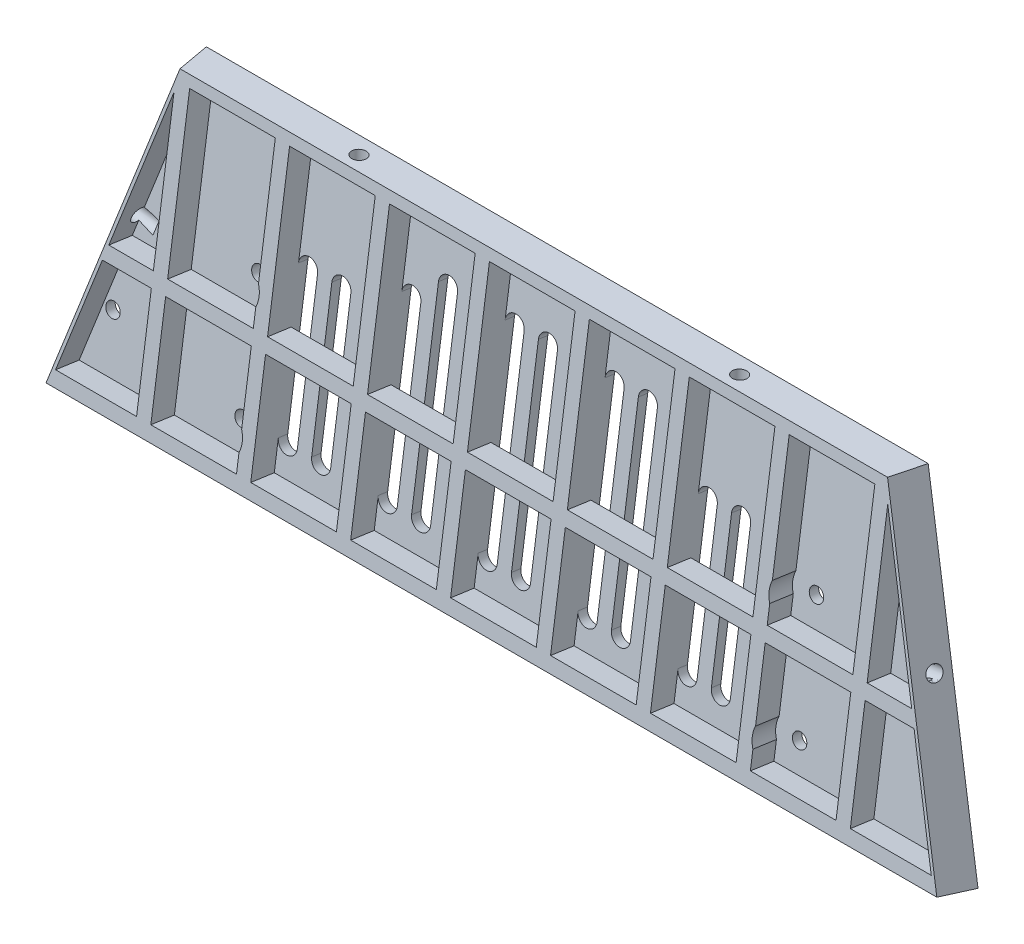
SolidWorks part; units mm, degrees
material "ABS"
ref_plane "前视基准面" through (0, 0, 0) normal (0, 0, 1) x (1, 0, 0)
ref_plane "上视基准面" through (0, 0, 0) normal (0, 1, 0) x (1, 0, 0)
ref_plane "右视基准面" through (0, 0, 0) normal (1, 0, 0) x (0, 0, -1)
other "Configuration Table"
sketch "草图1" plane through (0, 0, 0) normal (0, 0, 1) x (1, 0, 0)
  line L0 (145, -15) -> (145, -95)
  line L1 (145, -95) -> (-145, -95)
  line L2 (-145, -95) -> (-145, -15)
  line L3 (-145, -15) -> (-85, 215)
  line L4 (-85, 215) -> (85, 215)
  line L5 (85, 215) -> (145, -15)
  line L6 (0, 215) -> (0, -95) construction
  arc A0 (145, -95) -> (-145, -95) centre (0, 951.25) cw construction
  point P11 (0, -105)
  dimension "D4" = 320
  dimension "D1" = 10
  dimension "D2" = 290
  dimension "D3" = 80
  dimension "D5" = 170
  dimension "D6" = 95
extrude "凸台-拉伸1" add sketch "草图1" against normal blind 70
chamfer "倒角1" distance 70 angle 18 4 edges at (115, 100, -70) (145, -55, -70) (-115, 100, -70) (-145, -55, -70)
sketch "草图2" plane through (0, 0, 0) normal (1, 0, 0) x (0, 0, -1)
  line L0 (10, 215) -> (0, 145)
  line L1 (70, 215) -> (0, 215) construction
  line L2 (0, 215) -> (0, -15) construction
  line L3 (0, 145) -> (0, 215)
  line L4 (0, 215) -> (10, 215)
  dimension "D1" = 70
  dimension "D2" = 10
extrude "切除-拉伸1" cut sketch "草图2" against normal through all and the other way through all
chamfer "倒角2" distance 20 distance2 60 1 edges at (0, 215, -70)
sketch "草图12" plane through (0, 2.9, 20.3) normal (0, 0.1414, 0.9899) x (1, 0, 0)
  line L4 (103.2609, 143.5427) -> (81.6421, 214.2534)
  line L5 (81.6421, 214.2534) -> (-81.6421, 214.2534)
  line L7 (-103.2609, 143.5427) -> (103.2609, 143.5427)
  line L9 (81.6421, 214.2534) -> (-81.6421, 214.2534)
  line L11 (-103.2609, 143.5427) -> (103.2609, 143.5427)
  line L12 (103.2609, 143.5427) -> (81.6421, 214.2534)
  line L14 (-81.6421, 214.2534) -> (-103.2609, 143.5427)
  line L15 (-81.6421, 214.2534) -> (-103.2609, 143.5427)
  dimension "D1" = 0
extrude "切除-拉伸10" cut sketch "草图12" against normal blind 110 flip side to cut
sketch "草图13" plane through (0, 2.9, 20.3) normal (0, 0.1414, 0.9899) x (1, 0, 0)
  line L4 (103.2609, 143.5427) -> (81.6421, 214.2534)
  line L5 (81.6421, 214.2534) -> (-81.6421, 214.2534)
  line L7 (-103.2609, 143.5427) -> (103.2609, 143.5427)
  line L9 (81.6421, 214.2534) -> (-81.6421, 214.2534)
  line L11 (-103.2609, 143.5427) -> (103.2609, 143.5427)
  line L12 (103.2609, 143.5427) -> (81.6421, 214.2534)
  line L14 (-81.6421, 214.2534) -> (-103.2609, 143.5427)
  line L15 (-81.6421, 214.2534) -> (-103.2609, 143.5427)
  dimension "D1" = 0
extrude "切除-拉伸11" cut sketch "草图13" against normal blind 110 from offset 2 offset against normal yes
sketch "草图14" plane through (0, 2.9, 20.3) normal (0, 0.1414, 0.9899) x (1, 0, 0)
  line L4 (-76.5908, 210.2534) -> (-96.0695, 146.5427)
  line L5 (-96.0695, 146.5427) -> (96.0695, 146.5427)
  line L6 (96.0695, 146.5427) -> (76.5908, 210.2534)
  line L7 (76.5908, 210.2534) -> (-76.5908, 210.2534)
  line L8 (-103.2609, 143.5427) -> (103.2609, 143.5427) construction
  line L9 (81.6421, 214.2534) -> (-81.6421, 214.2534) construction
  line L11 (103.2609, 143.5427) -> (81.6421, 214.2534) construction
  line L23 (0, 214.2534) -> (0, 143.5427) construction
  dimension "D1" = 3
  dimension "D2" = 4
  dimension "D3" = 6
extrude "切除-拉伸12" cut sketch "草图14" against normal blind 110 flip side to cut
sketch "草图15" plane through (0, 2.9, 20.3) normal (0, 0.1414, 0.9899) x (1, 0, 0)
  line L0 (0, 210.2534) -> (0, 146.5427) construction
  line L1 (76.5908, 210.2534) -> (-76.5908, 210.2534) construction
  line L2 (-96.0695, 146.5427) -> (96.0695, 146.5427) construction
  line L3 (77.7153, 189.4741) -> (86.4866, 160.785) construction
  line L4 (-25, 205.2534) -> (25, 205.2534) construction
  line L5 (96.0695, 146.5427) -> (76.5908, 210.2534) construction
  line L6 (76.5908, 210.2534) -> (71.8093, 208.7915) construction
  line L7 (71.8093, 208.7915) -> (77.7153, 189.4741) construction
  line L8 (0, 195.5427) -> (0, 155.5427) construction
  line L9 (2, 195.5427) -> (2, 155.5427)
  line L10 (-2, 195.5427) -> (-2, 155.5427)
  line L11 (7, 155.5427) -> (7, 195.5427) construction
  line L12 (5, 155.5427) -> (5, 195.5427)
  line L13 (9, 155.5427) -> (9, 195.5427)
  line L14 (14, 155.5427) -> (14, 195.5427) construction
  line L15 (12, 155.5427) -> (12, 195.5427)
  line L16 (16, 155.5427) -> (16, 195.5427)
  line L17 (21, 155.5427) -> (21, 195.5427) construction
  line L18 (19, 155.5427) -> (19, 195.5427)
  line L19 (23, 155.5427) -> (23, 195.5427)
  line L20 (28, 155.5427) -> (28, 190.5427) construction
  line L21 (26, 155.5427) -> (26, 190.5427)
  line L22 (30, 155.5427) -> (30, 190.5427)
  line L23 (35, 155.5427) -> (35, 185.5427) construction
  line L24 (33, 155.5427) -> (33, 185.5427)
  line L25 (37, 155.5427) -> (37, 185.5427)
  line L26 (42, 185.5427) -> (42, 155.5427) construction
  line L27 (44, 185.5427) -> (44, 155.5427)
  line L28 (40, 185.5427) -> (40, 155.5427)
  line L29 (49, 185.5427) -> (49, 155.5427) construction
  line L30 (51, 185.5427) -> (51, 155.5427)
  line L31 (47, 185.5427) -> (47, 155.5427)
  line L32 (21, 195.5427) -> (35, 185.5427) construction
  line L33 (0, 195.5427) -> (7, 195.5427) construction
  line L34 (7, 195.5427) -> (14, 195.5427) construction
  line L35 (14, 195.5427) -> (21, 195.5427) construction
  line L36 (35, 185.5427) -> (42, 185.5427) construction
  line L37 (42, 185.5427) -> (49, 185.5427) construction
  line L38 (35, 185.5427) -> (28, 185.5427) construction
  line L39 (28, 185.5427) -> (21, 185.5427) construction
  line L40 (0, 155.5427) -> (7, 155.5427) construction
  line L41 (7, 155.5427) -> (14, 155.5427) construction
  line L42 (14, 155.5427) -> (21, 155.5427) construction
  line L43 (21, 155.5427) -> (28, 155.5427) construction
  line L44 (28, 155.5427) -> (35, 155.5427) construction
  line L45 (35, 155.5427) -> (42, 155.5427) construction
  line L46 (42, 155.5427) -> (49, 155.5427) construction
  line L47 (-2, 175.5427) -> (2, 175.5427) construction
  line L48 (5, 175.5427) -> (9, 175.5427) construction
  line L49 (12, 175.5427) -> (16, 175.5427) construction
  line L50 (19, 175.5427) -> (23, 175.5427) construction
  line L51 (26, 173.0427) -> (30, 173.0427) construction
  line L52 (33, 170.5427) -> (37, 170.5427) construction
  line L53 (40, 170.5427) -> (44, 170.5427) construction
  line L54 (47, 170.5427) -> (51, 170.5427) construction
  circle A0 centre (77.7153, 189.4741) radius 1.5
  circle A1 centre (86.4866, 160.785) radius 1.5
  circle A2 centre (-25, 205.2534) radius 1.5
  circle A3 centre (25, 205.2534) radius 1.5
  circle A4 centre (-86.4866, 160.785) radius 1.5
  circle A5 centre (-77.7153, 189.4741) radius 1.5
  arc A6 (2, 195.5427) -> (-2, 195.5427) centre (0, 195.5427) ccw
  arc A7 (-2, 155.5427) -> (2, 155.5427) centre (0, 155.5427) ccw
  arc A8 (5, 155.5427) -> (9, 155.5427) centre (7, 155.5427) ccw
  arc A9 (9, 195.5427) -> (5, 195.5427) centre (7, 195.5427) ccw
  arc A10 (12, 155.5427) -> (16, 155.5427) centre (14, 155.5427) ccw
  arc A11 (16, 195.5427) -> (12, 195.5427) centre (14, 195.5427) ccw
  arc A12 (19, 155.5427) -> (23, 155.5427) centre (21, 155.5427) ccw
  arc A13 (23, 195.5427) -> (19, 195.5427) centre (21, 195.5427) ccw
  arc A14 (26, 155.5427) -> (30, 155.5427) centre (28, 155.5427) ccw
  arc A15 (30, 190.5427) -> (26, 190.5427) centre (28, 190.5427) ccw
  arc A16 (33, 155.5427) -> (37, 155.5427) centre (35, 155.5427) ccw
  arc A17 (37, 185.5427) -> (33, 185.5427) centre (35, 185.5427) ccw
  arc A18 (44, 185.5427) -> (40, 185.5427) centre (42, 185.5427) ccw
  arc A19 (40, 155.5427) -> (44, 155.5427) centre (42, 155.5427) ccw
  arc A20 (51, 185.5427) -> (47, 185.5427) centre (49, 185.5427) ccw
  arc A21 (47, 155.5427) -> (51, 155.5427) centre (49, 155.5427) ccw
  point P25 (0, 175.5427)
  point P30 (7, 175.5427)
  point P37 (14, 175.5427)
  point P44 (21, 175.5427)
  point P51 (28, 173.0427)
  point P58 (35, 170.5427)
  point P65 (42, 170.5427)
  point P72 (49, 170.5427)
  dimension "D1" = 3
  dimension "D8" = 4
  dimension "D7" = 9
  dimension "D2" = 5
  dimension "D3" = 30
  dimension "D4" = 20.2
  dimension "D5" = 50
  dimension "D6" = 5
  dimension "D9" = 40
  dimension "D10" = 3
  dimension "D11" = 30
extrude "切除-拉伸13" cut sketch "草图15" against normal blind 10
sketch "草图16" plane through (0, 2.9, 20.3) normal (0, 0.1414, 0.9899) x (1, 0, 0)
  line L0 (0, 210.2534) -> (0, 146.5427) construction
  line L1 (76.5908, 210.2534) -> (-76.5908, 210.2534) construction
  line L2 (-96.0695, 146.5427) -> (96.0695, 146.5427) construction
  line L3 (58.5908, 180.2534) -> (58.5908, 155.2534) construction
  line L5 (-42.5, 193.2534) -> (42.5, 193.2534) construction
  line L6 (58.5908, 155.2534) -> (58.5908, 146.5427) construction
  line L7 (58.5908, 180.2534) -> (58.5908, 210.2534) construction
  circle A0 centre (58.5908, 180.2534) radius 1.5
  circle A1 centre (58.5908, 155.2534) radius 1.5
  circle A2 centre (-58.5908, 155.2534) radius 1.5
  circle A3 centre (-58.5908, 180.2534) radius 1.5
  circle A4 centre (42.5, 193.2534) radius 1.5 construction
  circle A5 centre (-42.5, 193.2534) radius 1.5 construction
  dimension "D1" = 3
  dimension "D5" = 3
  dimension "D2" = 30
  dimension "D3" = 25
  dimension "D4" = 18
  dimension "D6" = 17
  dimension "D7" = 85
extrude "切除-拉伸14" cut sketch "草图16" against normal blind 10
mirror "镜向2" about plane through (0, 0, 0) normal (1, 0, 0) of "切除-拉伸13"
sketch "草图17" plane through (0, 2.9, 20.3) normal (0, 0.1414, 0.9899) x (1, 0, 0)
  line L0 (-76.5908, 210.2534) -> (-96.0695, 146.5427) construction
  line L1 (76.5908, 207.2534) -> (-76.5908, 207.2534)
  line L2 (76.5908, 207.2534) -> (76.5908, 210.2534)
  line L3 (76.5908, 210.2534) -> (-76.5908, 210.2534)
  line L4 (-76.5908, 207.2534) -> (-76.5908, 210.2534)
  line L5 (76.5908, 207.2534) -> (-76.5908, 210.2534) construction
  line L6 (76.5908, 210.2534) -> (-76.5908, 207.2534) construction
  line L7 (76.5908, 210.2534) -> (-76.5908, 210.2534) construction
  line L8 (9, 155.5427) -> (9, 195.5427) construction
  line L9 (12, 207.2534) -> (9, 207.2534)
  line L10 (12, 207.2534) -> (12, 149.5427)
  line L11 (12, 149.5427) -> (9, 149.5427)
  line L12 (9, 207.2534) -> (9, 149.5427)
  line L13 (12, 207.2534) -> (9, 149.5427) construction
  line L14 (12, 149.5427) -> (9, 207.2534) construction
  line L15 (12, 195.5427) -> (12, 155.5427) construction
  line L16 (96.0695, 146.5427) -> (76.5908, 210.2534) construction
  line L17 (95.1523, 149.5427) -> (-95.1523, 149.5427)
  line L18 (95.1523, 149.5427) -> (95.1523, 146.5427)
  line L19 (95.1523, 146.5427) -> (-95.1523, 146.5427)
  line L20 (-95.1523, 149.5427) -> (-95.1523, 146.5427)
  line L21 (95.1523, 149.5427) -> (-95.1523, 146.5427) construction
  line L22 (95.1523, 146.5427) -> (-95.1523, 149.5427) construction
  line L23 (-96.0695, 146.5427) -> (96.0695, 146.5427) construction
  line L24 (33, 207.2534) -> (33, 149.5427)
  line L25 (33, 207.2534) -> (30, 207.2534)
  line L26 (30, 207.2534) -> (30, 149.5427)
  line L27 (33, 149.5427) -> (30, 149.5427)
  line L28 (54, 207.2534) -> (54, 149.5427)
  line L29 (54, 207.2534) -> (51, 207.2534)
  line L30 (51, 207.2534) -> (51, 149.5427)
  line L31 (54, 149.5427) -> (51, 149.5427)
  line L32 (75, 207.2534) -> (75, 149.5427)
  line L33 (75, 207.2534) -> (72, 207.2534)
  line L34 (72, 207.2534) -> (72, 149.5427)
  line L35 (75, 149.5427) -> (72, 149.5427)
  line L48 (76.5908, 210.2534) -> (95.1523, 149.5427)
  line L49 (92.0152, 149.5427) -> (74.371, 207.2534)
  line L51 (117, 207.2534) -> (117, 149.5427) [skipped]
  line L52 (117, 207.2534) -> (114, 207.2534) [skipped]
  line L53 (114, 207.2534) -> (114, 149.5427) [skipped]
  line L54 (117, 149.5427) -> (114, 149.5427) [skipped]
  line L55 (138, 207.2534) -> (138, 149.5427) [skipped]
  line L56 (138, 207.2534) -> (135, 207.2534) [skipped]
  line L57 (135, 207.2534) -> (135, 149.5427) [skipped]
  line L58 (138, 149.5427) -> (135, 149.5427) [skipped]
  line L59 (96, 207.2534) -> (96, 149.5427) [skipped]
  line L60 (96, 149.5427) -> (93, 149.5427) [skipped]
  line L61 (93, 207.2534) -> (93, 149.5427) [skipped]
  line L62 (96, 207.2534) -> (93, 207.2534) [skipped]
  circle A0 centre (58.5908, 180.2534) radius 5
  circle A1 centre (58.5908, 155.2534) radius 5
  circle A2 centre (58.5908, 180.2534) radius 1.5 construction
  circle A3 centre (58.5908, 155.2534) radius 1.5 construction
  point P4 (0, 208.7534)
  point P14 (10.5, 178.398)
  point P23 (0, 148.0427)
  dimension "D5" = 10
  dimension "D1" = 3
  dimension "D2" = 3
  dimension "D4" = 18
  dimension "D6" = 3
  dimension "D3" = 7
extrude "凸台-拉伸2" add sketch "草图17" along normal blind 5 contours L1 L12 L11 L10 | L1 L26 L17 L24 | A1 L28 A0 L1 L30 L17 | L32 L49 L33 L34 L17 | L49 L17 L48 L2 L1 L32 | L17 L20 L19 L18 L11 | L4 L1 L33 L2 L3 | L49 L32 L1
mirror "镜向4" about plane through (0, 0, 0) normal (1, 0, 0) of "凸台-拉伸2"
sketch "草图18" plane through (0, 2.9, 20.3) normal (0, 0.1414, 0.9899) x (1, 0, 0)
  line L0 (76.5908, 210.2534) -> (95.1523, 149.5427) construction
  line L1 (-87.5089, 174.5427) -> (87.5089, 174.5427)
  line L2 (-87.5089, 174.5427) -> (-87.5089, 171.5427)
  line L3 (-87.5089, 171.5427) -> (87.5089, 171.5427)
  line L4 (87.5089, 174.5427) -> (87.5089, 171.5427)
  line L5 (-87.5089, 174.5427) -> (87.5089, 171.5427) construction
  line L6 (-87.5089, 171.5427) -> (87.5089, 174.5427) construction
  line L7 (-76.5908, 210.2534) -> (-95.1523, 149.5427) construction
  line L8 (95.1523, 146.5427) -> (-95.1523, 146.5427) construction
  point P4 (0, 173.0427)
  dimension "D1" = 3
  dimension "D2" = 25
extrude "凸台-拉伸3" add sketch "草图18" along normal blind 5
chamfer "倒角3" distance 7 angle 5.95 1 edges at (0, 211.7473, -4.4846)
sketch "草图21" plane through (0, 210.8863, -8.0281) normal (0, 0.9993, -0.038) x (1, 0, 0)
  circle A1 centre (40, -0.3868) radius 1.5
  circle A2 centre (-40, -0.3868) radius 1.5
extrude "切除-拉伸17" cut sketch "草图21" against normal blind 5
chamfer "倒角4" distance 10 angle 13.26 2 edges at (85.9831, 181.3359, -0.1401) (-85.9831, 181.3359, -0.1401)
sketch "草图23" plane through (-125.3632, 42.3116, 25.1612) normal (-0.9308, 0.3142, 0.1868) x (0.177, -0.0597, 0.9824)
  ellipse E1 centre (-29.724, 144.0929) end of major axis (-31.2043, 143.8509) minor radius 1.5
extrude "切除-拉伸19" cut sketch "草图23" against normal blind 5
sketch "草图24" plane through (125.3632, 42.3116, 25.1612) normal (0.9308, 0.3142, 0.1868) x (0.177, 0.0597, -0.9824)
  ellipse E1 centre (29.724, 144.0929) end of major axis (31.2043, 143.8509) minor radius 1.5
extrude "切除-拉伸20" cut sketch "草图24" against normal blind 5
